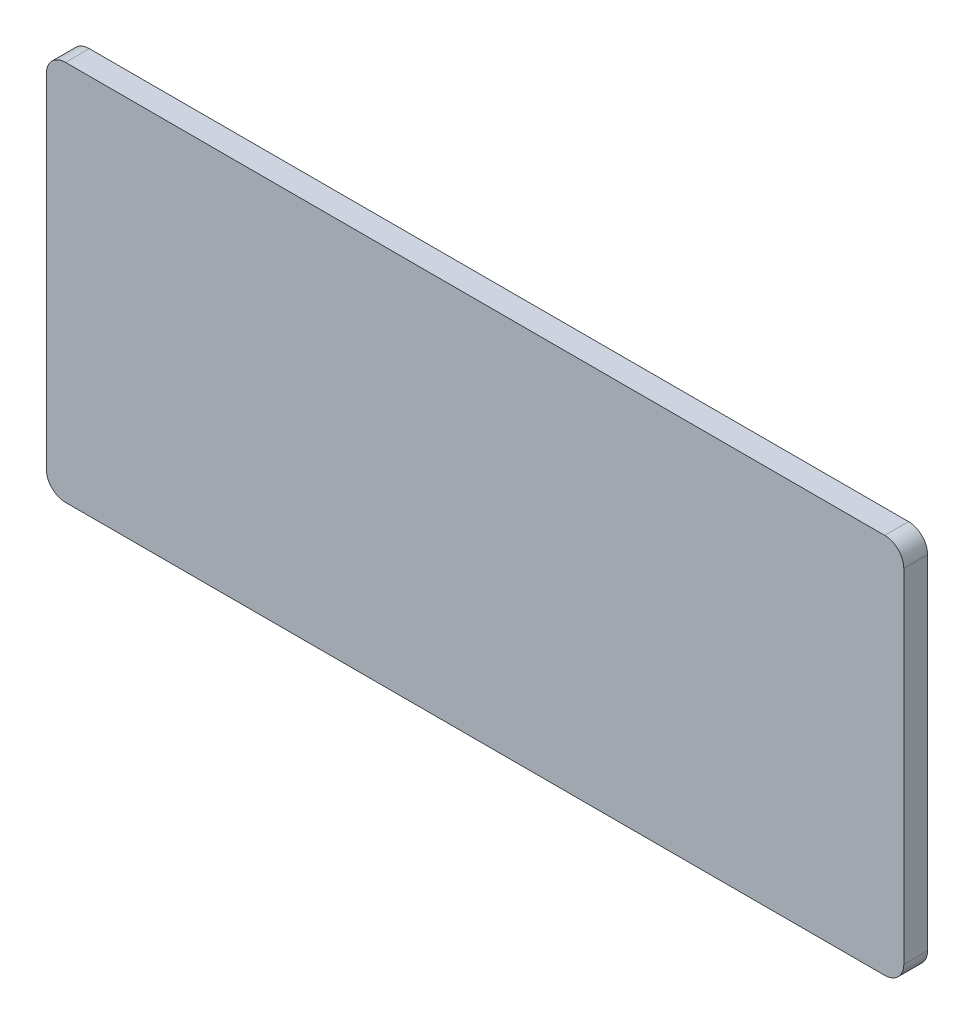
SolidWorks part; units mm, degrees
material "Custom Plastic"
ref_plane "X-Y Datum" through (0, 0, 0) normal (0, 0, 1) x (1, 0, 0)
ref_plane "X-Z Datum" through (0, 0, 0) normal (0, 1, 0) x (1, 0, 0)
ref_plane "Y-Z Datum" through (0, 0, 0) normal (1, 0, 0) x (0, 0, -1)
sketch "Sketch1" plane through (0, 0, 0) normal (0, 0, 1) x (1, 0, 0)
  line L1 (-57.15, -25.4) -> (57.15, -25.4)
  line L2 (-57.15, -25.4) -> (-57.15, 25.4)
  line L3 (-57.15, 25.4) -> (57.15, 25.4)
  line L4 (57.15, -25.4) -> (57.15, 25.4)
  line L5 (-57.15, -25.4) -> (57.15, 25.4) construction
  line L6 (-57.15, 25.4) -> (57.15, -25.4) construction
  point P0 (0, 0)
  dimension "D1" = 50.8
  dimension "D2" = 114.3
extrude "Boss-Extrude1" add sketch "Sketch1" along normal blind 3.175
fillet "Fillet1" radius 2.54 4 edges at (-57.15, -25.4, 1.5875) (-57.15, 25.4, 1.5875) (57.15, -25.4, 1.5875) (57.15, 25.4, 1.5875)
